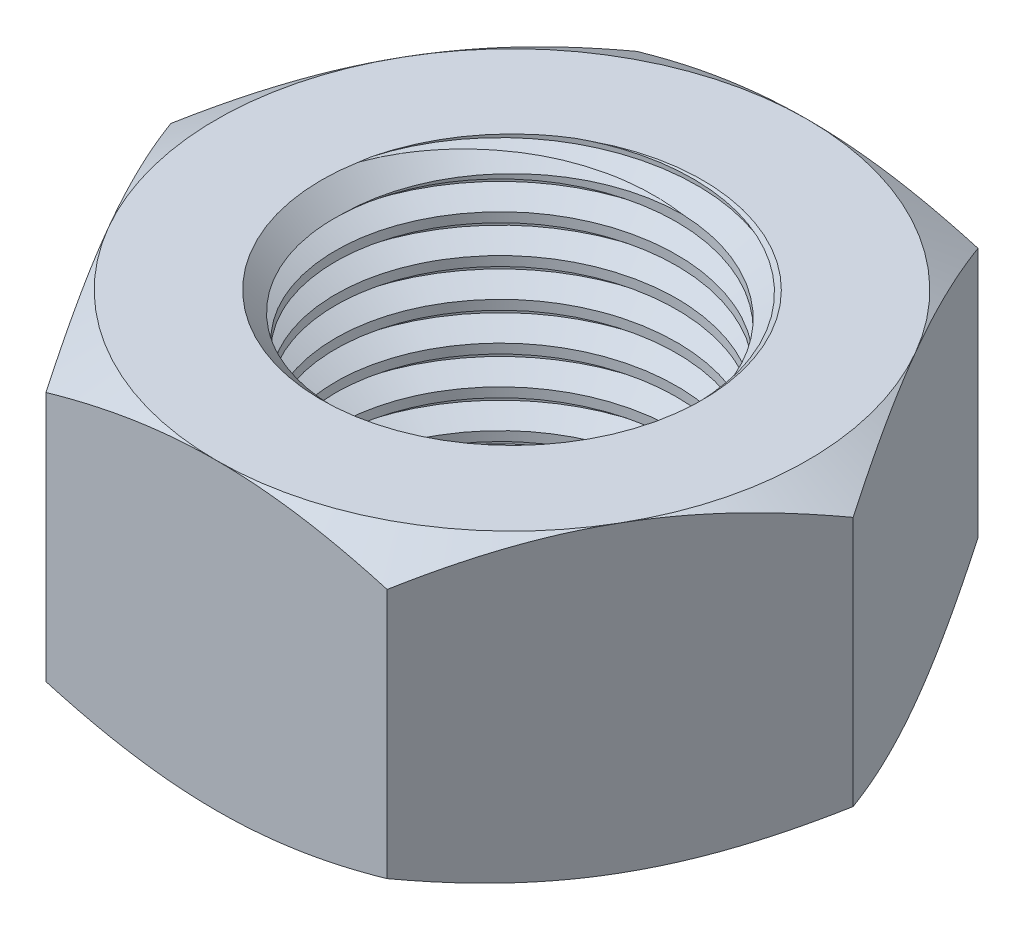
SolidWorks part; units mm, degrees
ref_plane "Front Plane" through (0, 0, 0) normal (0, 0, 1) x (1, 0, 0)
ref_plane "Top Plane" through (0, 0, 0) normal (0, 1, 0) x (1, 0, 0)
ref_plane "Right Plane" through (0, 0, 0) normal (1, 0, 0) x (0, 0, -1)
sketch "Sketch1" plane through (0, 0, 0) normal (0, 1, 0) x (1, 0, 0)
  line L1 (4.5, -7.7942) -> (9, 0)
  line L2 (9, 0) -> (4.5, 7.7942)
  line L3 (4.5, 7.7942) -> (-4.5, 7.7942)
  line L4 (-4.5, 7.7942) -> (-9, 0)
  line L5 (-9, 0) -> (-4.5, -7.7942)
  line L6 (-4.5, -7.7942) -> (4.5, -7.7942)
  circle A0 centre (0, 0) radius 7.7942 construction
  dimension "D1" = 18
extrude "Boss-Extrude1" add sketch "Sketch1" along normal blind 8
sketch "Sketch2" plane through (0, 0, 0) normal (1, 0, 0) x (0, 0, -1)
  line L0 (0, -1000) -> (0, 49000) construction
  line L1 (7.7942, 0) -> (11.855, 0)
  line L2 (11.855, 0) -> (11.855, 2.3445)
  line L3 (11.855, 2.3445) -> (7.7942, 0)
  line L4 (-992.2058, 4) -> (49007.7942, 4) construction
  line L5 (7.7942, 8) -> (7.7942, 0) construction
  line L6 (11.855, 5.6555) -> (7.7942, 8)
  line L7 (11.855, 8) -> (11.855, 5.6555)
  line L8 (7.7942, 8) -> (11.855, 8)
  point P13 (7.7942, 4)
  dimension "D1" = 30
revolve "Cut-Revolve1" cut sketch "Sketch2" angle 360 about L0
hole_wizard "M10x1.0 Tapped Hole3" positions "Sketch7" profile "Sketch8" tap size "M10x1.0" standard "ANSI Metric" end condition up to next
sketch "Sketch7" plane through (0, 8, 0) normal (0, 1, 0) x (1, 0, 0)
  point P0 (0, 0)
sketch "Sketch8" plane through (0, 8, 0) normal (1, 0, 0) x (0, 0, 1)
  line L0 (0, 0) -> (0, 8)
  line L1 (0, 8) -> (4.5, 8)
  line L2 (4.5, 8) -> (4.5, 0.525)
  line L3 (4.5, 0.525) -> (5.025, 0)
  line L5 (5.025, 0) -> (0, 0)
  line L6 (-4.5, 0.525) -> (-5.025, 0) construction
  line L11 (0, -6.35) -> (0, 107.95) construction
  dimension "Thru Tap Drill Dia." = 9
  dimension "Thru Tap Drill Depth" = 8
  dimension "Near C'Sink Dia." = 10.05
  dimension "Near C'Sink Angle" = 90
cosmetic thread "Hole Thread2" parameters "D2"=10
thread "Thread1" pitch 1 method cut profile "Thread Profile1" start angle 0, offset 1, length 0, pitch 1, diameter 9
ref_plane "Plane1" through (-4.5, 8.475, 0) normal (0, 0, 1) x (-1, 0, 0)
sketch "Thread Profile1" plane through (-4.5, 8.475, 0) normal (0, 0, 1) x (-1, 0, 0)
  line L0 (0, 0) -> (0, 1) construction
  line L1 (0, 0) -> (0.5413, 0.3125)
  line L2 (0.5413, 0.3125) -> (0.5413, 0.4375)
  line L3 (0.5413, 0.4375) -> (0, 0.75)
  line L4 (0.5413, 0.375) -> (0, 0.375) construction
  line L11 (0, 0) -> (0, 0.75)
  point P2 (0, 0)
  dimension "Pitch" = 1
  dimension "Profile_Angle" = 60
  dimension "Profile_Land" = 0.125
  dimension "Profile_Height" = 0.5413
